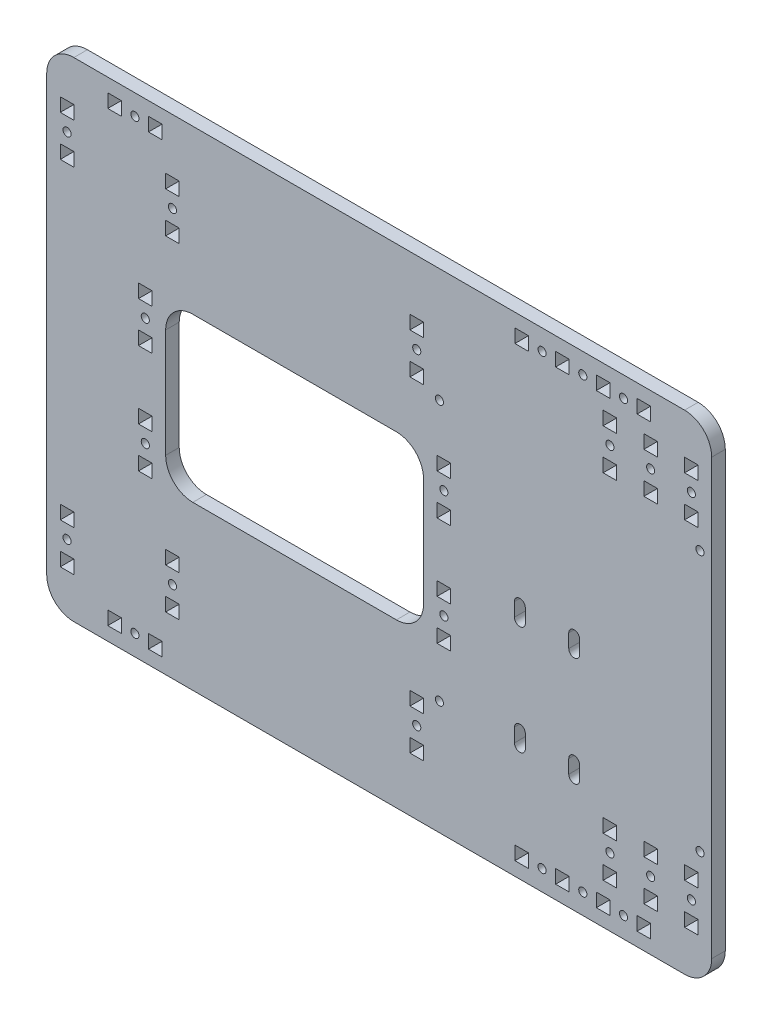
SolidWorks part; units mm, degrees
ref_plane "Front Plane" through (0, 0, 0) normal (0, 0, 1) x (1, 0, 0)
ref_plane "Top Plane" through (0, 0, 0) normal (0, 1, 0) x (1, 0, 0)
ref_plane "Right Plane" through (0, 0, 0) normal (1, 0, 0) x (0, 0, -1)
sketch "Sketch1" plane through (0, 0, 0) normal (0, 0, 1) x (1, 0, 0)
  line L0 (0, 0) -> (264.3375, 0) construction
  line L1 (-91.3244, 90) -> (153.676, 90)
  line L3 (-91.3244, -90) -> (153.676, -90)
  line L5 (23.6756, 97.7888) -> (23.6756, -107.1048) construction
  line L6 (-92.4996, 82.5) -> (92.5, 82.5) construction
  line L7 (92.5, -82.5) -> (-92.4996, -82.5) construction
  line L8 (-91.3244, 90) -> (-91.3244, -90)
  line L17 (53.355, -48) -> (53.355, 48) construction
  line L29 (53.355, -48) -> (149.355, -48) construction
  line L49 (53.355, 48) -> (149.355, 48) construction
  line L50 (149.355, -48) -> (149.355, 48) construction
  line L51 (-83.8244, 77.0051) -> (-83.8244, -67.4641) construction
  line L97 (-47.5, 30) -> (47.5, 30)
  line L98 (-47.5, 30) -> (-47.5, -30)
  line L99 (-47.5, -30) -> (47.5, -30)
  line L100 (47.5, 30) -> (47.5, -30)
  line L105 (103, -45) -> (49.07, -45) construction
  line L106 (103, -4.9002) -> (73.57, -4.9002) construction
  line L107 (103, -4.9002) -> (103, -45) construction
  line L108 (103, -7.4002) -> (103, -2.4002) construction
  line L109 (101, -7.4002) -> (101, -2.4002)
  line L110 (105, -7.4002) -> (105, -2.4002)
  line L111 (83, -7.4002) -> (83, -2.4002) construction
  line L112 (81, -7.4002) -> (81, -2.4002)
  line L113 (85, -7.4002) -> (85, -2.4002)
  line L114 (83, -47.5) -> (83, -42.5) construction
  line L115 (81, -47.5) -> (81, -42.5)
  line L116 (85, -47.5) -> (85, -42.5)
  line L117 (103, -47.5) -> (103, -42.5) construction
  line L118 (101, -47.5) -> (101, -42.5)
  line L119 (105, -47.5) -> (105, -42.5)
  line L122 (153.676, 90) -> (153.676, -90)
  line L124 (-83.8244, 65) -> (153.676, 65) construction
  line L125 (-83.8244, -65) -> (153.676, -65) construction
  line L126 (55, -20) -> (55, 20) construction
  arc A4 (101, -7.4002) -> (105, -7.4002) centre (103, -7.4002) ccw
  arc A5 (105, -2.4002) -> (101, -2.4002) centre (103, -2.4002) ccw
  arc A6 (81, -7.4002) -> (85, -7.4002) centre (83, -7.4002) ccw
  arc A7 (85, -2.4002) -> (81, -2.4002) centre (83, -2.4002) ccw
  arc A8 (81, -47.5) -> (85, -47.5) centre (83, -47.5) ccw
  arc A9 (85, -42.5) -> (81, -42.5) centre (83, -42.5) ccw
  arc A10 (101, -47.5) -> (105, -47.5) centre (103, -47.5) ccw
  arc A11 (105, -42.5) -> (101, -42.5) centre (103, -42.5) ccw
  circle A12 centre (53.355, 48) radius 1.5
  circle A13 centre (149.355, 48) radius 1.5
  circle A14 centre (149.355, -48) radius 1.5
  circle A15 centre (53.355, -48) radius 1.5
  point P113 (103, -4.9002)
  point P122 (83, -4.9002)
  point P129 (83, -45)
  point P136 (103, -45)
  line B0 (-63.8248, 82.5) -> (-53.8248, 82.5) construction
  line B1 (-63.8248, 85) -> (-68.8248, 85)
  line B2 (-63.8248, 85) -> (-63.8248, 80)
  line B3 (-63.8248, 80) -> (-68.8248, 80)
  line B4 (-68.8248, 85) -> (-68.8248, 80)
  line B5 (-53.8248, 85) -> (-48.8248, 85)
  line B6 (-53.8248, 85) -> (-53.8248, 80)
  line B7 (-53.8248, 80) -> (-48.8248, 80)
  line B8 (-48.8248, 85) -> (-48.8248, 80)
  line B9 (-58.8248, 82.5) -> (-58.8248, 89.4724) construction
  circle B10 centre (-58.8248, 82.5) radius 1.5
  line B11 (111.176, 82.5) -> (101.176, 82.5) construction
  line B12 (111.176, 85) -> (116.176, 85)
  line B13 (111.176, 85) -> (111.176, 80)
  line B14 (111.176, 80) -> (116.176, 80)
  line B15 (116.176, 85) -> (116.176, 80)
  line B16 (101.176, 85) -> (96.176, 85)
  line B17 (101.176, 85) -> (101.176, 80)
  line B18 (101.176, 80) -> (96.176, 80)
  line B19 (96.176, 85) -> (96.176, 80)
  line B20 (106.176, 82.5) -> (106.176, 89.4724) construction
  circle B21 centre (106.176, 82.5) radius 1.5
  line B22 (111.176, -82.5) -> (101.176, -82.5) construction
  line B23 (111.176, -85) -> (116.176, -85)
  line B24 (111.176, -85) -> (111.176, -80)
  line B25 (111.176, -80) -> (116.176, -80)
  line B26 (116.176, -85) -> (116.176, -80)
  line B27 (101.176, -85) -> (96.176, -85)
  line B28 (101.176, -85) -> (101.176, -80)
  line B29 (101.176, -80) -> (96.176, -80)
  line B30 (96.176, -85) -> (96.176, -80)
  line B31 (106.176, -82.5) -> (106.176, -89.4724) construction
  circle B32 centre (106.176, -82.5) radius 1.5
  line B33 (-63.8248, -82.5) -> (-53.8248, -82.5) construction
  line B34 (-63.8248, -85) -> (-68.8248, -85)
  line B35 (-63.8248, -85) -> (-63.8248, -80)
  line B36 (-63.8248, -80) -> (-68.8248, -80)
  line B37 (-68.8248, -85) -> (-68.8248, -80)
  line B38 (-53.8248, -85) -> (-48.8248, -85)
  line B39 (-53.8248, -85) -> (-53.8248, -80)
  line B40 (-53.8248, -80) -> (-48.8248, -80)
  line B41 (-48.8248, -85) -> (-48.8248, -80)
  line B42 (-58.8248, -82.5) -> (-58.8248, -89.4724) construction
  circle B43 centre (-58.8248, -82.5) radius 1.5
  line B44 (55, 25) -> (55, 15) construction
  line B45 (57.5, 25) -> (57.5, 30)
  line B46 (57.5, 25) -> (52.5, 25)
  line B47 (52.5, 25) -> (52.5, 30)
  line B48 (57.5, 30) -> (52.5, 30)
  line B49 (57.5, 15) -> (57.5, 10)
  line B50 (57.5, 15) -> (52.5, 15)
  line B51 (52.5, 15) -> (52.5, 10)
  line B52 (57.5, 10) -> (52.5, 10)
  line B53 (55, 20) -> (61.9724, 20) construction
  circle B54 centre (55, 20) radius 1.5
  line B55 (-55, 25) -> (-55, 15) construction
  line B56 (-57.5, 25) -> (-57.5, 30)
  line B57 (-57.5, 25) -> (-52.5, 25)
  line B58 (-52.5, 25) -> (-52.5, 30)
  line B59 (-57.5, 30) -> (-52.5, 30)
  line B60 (-57.5, 15) -> (-57.5, 10)
  line B61 (-57.5, 15) -> (-52.5, 15)
  line B62 (-52.5, 15) -> (-52.5, 10)
  line B63 (-57.5, 10) -> (-52.5, 10)
  line B64 (-55, 20) -> (-61.9724, 20) construction
  circle B65 centre (-55, 20) radius 1.5
  line B66 (55, -25) -> (55, -15) construction
  line B67 (57.5, -25) -> (57.5, -30)
  line B68 (57.5, -25) -> (52.5, -25)
  line B69 (52.5, -25) -> (52.5, -30)
  line B70 (57.5, -30) -> (52.5, -30)
  line B71 (57.5, -15) -> (57.5, -10)
  line B72 (57.5, -15) -> (52.5, -15)
  line B73 (52.5, -15) -> (52.5, -10)
  line B74 (57.5, -10) -> (52.5, -10)
  line B75 (55, -20) -> (61.9724, -20) construction
  circle B76 centre (55, -20) radius 1.5
  line B77 (-55, -25) -> (-55, -15) construction
  line B78 (-57.5, -25) -> (-57.5, -30)
  line B79 (-57.5, -25) -> (-52.5, -25)
  line B80 (-52.5, -25) -> (-52.5, -30)
  line B81 (-57.5, -30) -> (-52.5, -30)
  line B82 (-57.5, -15) -> (-57.5, -10)
  line B83 (-57.5, -15) -> (-52.5, -15)
  line B84 (-52.5, -15) -> (-52.5, -10)
  line B85 (-57.5, -10) -> (-52.5, -10)
  line B86 (-55, -20) -> (-61.9724, -20) construction
  circle B87 centre (-55, -20) radius 1.5
  line B88 (45, 65) -> (45, 55) construction
  line B89 (47.5, 65) -> (47.5, 70)
  line B90 (47.5, 65) -> (42.5, 65)
  line B91 (42.5, 65) -> (42.5, 70)
  line B92 (47.5, 70) -> (42.5, 70)
  line B93 (47.5, 55) -> (47.5, 50)
  line B94 (47.5, 55) -> (42.5, 55)
  line B95 (42.5, 55) -> (42.5, 50)
  line B96 (47.5, 50) -> (42.5, 50)
  line B97 (45, 60) -> (51.9724, 60) construction
  circle B98 centre (45, 60) radius 1.5
  line B99 (-45, 65) -> (-45, 55) construction
  line B100 (-47.5, 65) -> (-47.5, 70)
  line B101 (-47.5, 65) -> (-42.5, 65)
  line B102 (-42.5, 65) -> (-42.5, 70)
  line B103 (-47.5, 70) -> (-42.5, 70)
  line B104 (-47.5, 55) -> (-47.5, 50)
  line B105 (-47.5, 55) -> (-42.5, 55)
  line B106 (-42.5, 55) -> (-42.5, 50)
  line B107 (-47.5, 50) -> (-42.5, 50)
  line B108 (-45, 60) -> (-51.9724, 60) construction
  circle B109 centre (-45, 60) radius 1.5
  line B110 (45, -65) -> (45, -55) construction
  line B111 (47.5, -65) -> (47.5, -70)
  line B112 (47.5, -65) -> (42.5, -65)
  line B113 (42.5, -65) -> (42.5, -70)
  line B114 (47.5, -70) -> (42.5, -70)
  line B115 (47.5, -55) -> (47.5, -50)
  line B116 (47.5, -55) -> (42.5, -55)
  line B117 (42.5, -55) -> (42.5, -50)
  line B118 (47.5, -50) -> (42.5, -50)
  line B119 (45, -60) -> (51.9724, -60) construction
  circle B120 centre (45, -60) radius 1.5
  line B121 (-45, -65) -> (-45, -55) construction
  line B122 (-47.5, -65) -> (-47.5, -70)
  line B123 (-47.5, -65) -> (-42.5, -65)
  line B124 (-42.5, -65) -> (-42.5, -70)
  line B125 (-47.5, -70) -> (-42.5, -70)
  line B126 (-47.5, -55) -> (-47.5, -50)
  line B127 (-47.5, -55) -> (-42.5, -55)
  line B128 (-42.5, -55) -> (-42.5, -50)
  line B129 (-47.5, -50) -> (-42.5, -50)
  line B130 (-45, -60) -> (-51.9724, -60) construction
  circle B131 centre (-45, -60) radius 1.5
  line B132 (96.176, 82.5) -> (86.176, 82.5) construction
  line B133 (96.176, 85) -> (101.176, 85)
  line B134 (96.176, 85) -> (96.176, 80)
  line B135 (96.176, 80) -> (101.176, 80)
  line B136 (101.176, 85) -> (101.176, 80)
  line B137 (86.176, 85) -> (81.176, 85)
  line B138 (86.176, 85) -> (86.176, 80)
  line B139 (86.176, 80) -> (81.176, 80)
  line B140 (81.176, 85) -> (81.176, 80)
  line B141 (91.176, 82.5) -> (91.176, 89.4724) construction
  circle B142 centre (91.176, 82.5) radius 1.5
  line B143 (126.176, 82.5) -> (116.176, 82.5) construction
  line B144 (126.176, 85) -> (131.176, 85)
  line B145 (126.176, 85) -> (126.176, 80)
  line B146 (126.176, 80) -> (131.176, 80)
  line B147 (131.176, 85) -> (131.176, 80)
  line B148 (116.176, 85) -> (111.176, 85)
  line B149 (116.176, 85) -> (116.176, 80)
  line B150 (116.176, 80) -> (111.176, 80)
  line B151 (111.176, 85) -> (111.176, 80)
  line B152 (121.176, 82.5) -> (121.176, 89.4724) construction
  circle B153 centre (121.176, 82.5) radius 1.5
  line B154 (96.176, -82.5) -> (86.176, -82.5) construction
  line B155 (96.176, -85) -> (101.176, -85)
  line B156 (96.176, -85) -> (96.176, -80)
  line B157 (96.176, -80) -> (101.176, -80)
  line B158 (101.176, -85) -> (101.176, -80)
  line B159 (86.176, -85) -> (81.176, -85)
  line B160 (86.176, -85) -> (86.176, -80)
  line B161 (86.176, -80) -> (81.176, -80)
  line B162 (81.176, -85) -> (81.176, -80)
  line B163 (91.176, -82.5) -> (91.176, -89.4724) construction
  circle B164 centre (91.176, -82.5) radius 1.5
  line B165 (126.176, -82.5) -> (116.176, -82.5) construction
  line B166 (126.176, -85) -> (131.176, -85)
  line B167 (126.176, -85) -> (126.176, -80)
  line B168 (126.176, -80) -> (131.176, -80)
  line B169 (131.176, -85) -> (131.176, -80)
  line B170 (116.176, -85) -> (111.176, -85)
  line B171 (116.176, -85) -> (116.176, -80)
  line B172 (116.176, -80) -> (111.176, -80)
  line B173 (111.176, -85) -> (111.176, -80)
  line B174 (121.176, -82.5) -> (121.176, -89.4724) construction
  circle B175 centre (121.176, -82.5) radius 1.5
  line B176 (-83.8244, 70) -> (-83.8244, 60) construction
  line B177 (-86.3244, 70) -> (-86.3244, 75)
  line B178 (-86.3244, 70) -> (-81.3244, 70)
  line B179 (-81.3244, 70) -> (-81.3244, 75)
  line B180 (-86.3244, 75) -> (-81.3244, 75)
  line B181 (-86.3244, 60) -> (-86.3244, 55)
  line B182 (-86.3244, 60) -> (-81.3244, 60)
  line B183 (-81.3244, 60) -> (-81.3244, 55)
  line B184 (-86.3244, 55) -> (-81.3244, 55)
  line B185 (-83.8244, 65) -> (-90.7968, 65) construction
  circle B186 centre (-83.8244, 65) radius 1.5
  line B187 (-83.8244, -60) -> (-83.8244, -70) construction
  line B188 (-86.3244, -60) -> (-86.3244, -55)
  line B189 (-86.3244, -60) -> (-81.3244, -60)
  line B190 (-81.3244, -60) -> (-81.3244, -55)
  line B191 (-86.3244, -55) -> (-81.3244, -55)
  line B192 (-86.3244, -70) -> (-86.3244, -75)
  line B193 (-86.3244, -70) -> (-81.3244, -70)
  line B194 (-81.3244, -70) -> (-81.3244, -75)
  line B195 (-86.3244, -75) -> (-81.3244, -75)
  line B196 (-83.8244, -65) -> (-90.7968, -65) construction
  circle B197 centre (-83.8244, -65) radius 1.5
  line B198 (146.176, 70) -> (146.176, 60) construction
  line B199 (143.676, 70) -> (143.676, 75)
  line B200 (143.676, 70) -> (148.676, 70)
  line B201 (148.676, 70) -> (148.676, 75)
  line B202 (143.676, 75) -> (148.676, 75)
  line B203 (143.676, 60) -> (143.676, 55)
  line B204 (143.676, 60) -> (148.676, 60)
  line B205 (148.676, 60) -> (148.676, 55)
  line B206 (143.676, 55) -> (148.676, 55)
  line B207 (146.176, 65) -> (139.2036, 65) construction
  circle B208 centre (146.176, 65) radius 1.5
  line B209 (146.176, -60) -> (146.176, -70) construction
  line B210 (143.676, -60) -> (143.676, -55)
  line B211 (143.676, -60) -> (148.676, -60)
  line B212 (148.676, -60) -> (148.676, -55)
  line B213 (143.676, -55) -> (148.676, -55)
  line B214 (143.676, -70) -> (143.676, -75)
  line B215 (143.676, -70) -> (148.676, -70)
  line B216 (148.676, -70) -> (148.676, -75)
  line B217 (143.676, -75) -> (148.676, -75)
  line B218 (146.176, -65) -> (139.2036, -65) construction
  circle B219 centre (146.176, -65) radius 1.5
  line B220 (131.176, -60) -> (131.176, -70) construction
  line B221 (128.676, -60) -> (128.676, -55)
  line B222 (128.676, -60) -> (133.676, -60)
  line B223 (133.676, -60) -> (133.676, -55)
  line B224 (128.676, -55) -> (133.676, -55)
  line B225 (128.676, -70) -> (128.676, -75)
  line B226 (128.676, -70) -> (133.676, -70)
  line B227 (133.676, -70) -> (133.676, -75)
  line B228 (128.676, -75) -> (133.676, -75)
  line B229 (131.176, -65) -> (124.2036, -65) construction
  circle B230 centre (131.176, -65) radius 1.5
  line B231 (116.176, -60) -> (116.176, -70) construction
  line B232 (113.676, -60) -> (113.676, -55)
  line B233 (113.676, -60) -> (118.676, -60)
  line B234 (118.676, -60) -> (118.676, -55)
  line B235 (113.676, -55) -> (118.676, -55)
  line B236 (113.676, -70) -> (113.676, -75)
  line B237 (113.676, -70) -> (118.676, -70)
  line B238 (118.676, -70) -> (118.676, -75)
  line B239 (113.676, -75) -> (118.676, -75)
  line B240 (116.176, -65) -> (109.2036, -65) construction
  circle B241 centre (116.176, -65) radius 1.5
  line B242 (131.176, 70) -> (131.176, 60) construction
  line B243 (128.676, 70) -> (128.676, 75)
  line B244 (128.676, 70) -> (133.676, 70)
  line B245 (133.676, 70) -> (133.676, 75)
  line B246 (128.676, 75) -> (133.676, 75)
  line B247 (128.676, 60) -> (128.676, 55)
  line B248 (128.676, 60) -> (133.676, 60)
  line B249 (133.676, 60) -> (133.676, 55)
  line B250 (128.676, 55) -> (133.676, 55)
  line B251 (131.176, 65) -> (124.2036, 65) construction
  circle B252 centre (131.176, 65) radius 1.5
  line B253 (116.176, 70) -> (116.176, 60) construction
  line B254 (113.676, 70) -> (113.676, 75)
  line B255 (113.676, 70) -> (118.676, 70)
  line B256 (118.676, 70) -> (118.676, 75)
  line B257 (113.676, 75) -> (118.676, 75)
  line B258 (113.676, 60) -> (113.676, 55)
  line B259 (113.676, 60) -> (118.676, 60)
  line B260 (118.676, 60) -> (118.676, 55)
  line B261 (113.676, 55) -> (118.676, 55)
  line B262 (116.176, 65) -> (109.2036, 65) construction
  circle B263 centre (116.176, 65) radius 1.5
  dimension "D22" = 45
  dimension "D23" = 5
  dimension "D8" = 3
  dimension "D24" = 2
  dimension "D1" = 165
  dimension "D2" = 7.5
  dimension "D4" = 32.4996
  dimension "D5" = 32.5
  dimension "D6" = 96
  dimension "D7" = 96
  dimension "D9" = 115
  dimension "D10" = 23.6756
  dimension "D11" = 28
  dimension "D12" = 47.5
  dimension "D13" = 7.5
  dimension "D14" = 25
  dimension "D15" = 40
  dimension "D16" = 95
  dimension "D17" = 60
  dimension "D18" = 7.5
  dimension "D19" = 15
  dimension "D20" = 15
  dimension "D21" = 7.5
  dimension "D25" = 2
  dimension "D27" = 20
  dimension "D33" = 60
  dimension "D26" = 2
sketch_block_instance "Trou M3 plots 5mm-1"
sketch_block "Trou M3 plots 5mm" parameters "D2"=3, "D1"=5, "D3"=5, "D4"=10
sketch_block_instance "Trou M3 plots 5mm-3"
sketch_block_instance "Trou M3 plots 5mm-4"
sketch_block_instance "Trou M3 plots 5mm-5"
sketch_block_instance "Trou M3 plots 5mm-7"
sketch_block_instance "Trou M3 plots 5mm-8"
sketch_block_instance "Trou M3 plots 5mm-9"
sketch_block_instance "Trou M3 plots 5mm-10"
sketch_block_instance "Trou M3 plots 5mm-11"
sketch_block_instance "Trou M3 plots 5mm-12"
sketch_block_instance "Trou M3 plots 5mm-13"
sketch_block_instance "Trou M3 plots 5mm-14"
sketch_block_instance "Trou M3 plots 5mm-15"
sketch_block_instance "Trou M3 plots 5mm-16"
sketch_block_instance "Trou M3 plots 5mm-18"
sketch_block_instance "Trou M3 plots 5mm-19"
sketch_block_instance "Trou M3 plots 5mm-20"
sketch_block_instance "Trou M3 plots 5mm-21"
sketch_block_instance "Trou M3 plots 5mm-22"
sketch_block_instance "Trou M3 plots 5mm-23"
sketch_block_instance "Trou M3 plots 5mm-24"
sketch_block_instance "Trou M3 plots 5mm-25"
sketch_block_instance "Trou M3 plots 5mm-26"
sketch_block_instance "Trou M3 plots 5mm-27"
extrude "Boss-Extrude1" add sketch "Sketch1" along normal blind 5 contours L122 L1 L8 L3 B175 B169 B166 B167 B168 B164 B144 B147 B146 B145 B142 B140 B137 B138 B139 B131 B125 B122 B123 B124 B111 B114 B113 B112 B109 B107 B104 B105 B106 B98 B92 B89 B90 B91 region at (31.1758, 86.9598, 0)
fillet "Fillet1" radius 10 8 edges at (-91.3244, 90, 2.5) (-91.3244, -90, 2.5) (153.676, 90, 2.5) (153.676, -90, 2.5) (-47.5, -30, 2.5) (-47.5, 30, 2.5) (47.5, 30, 2.5) (47.5, -30, 2.5)
